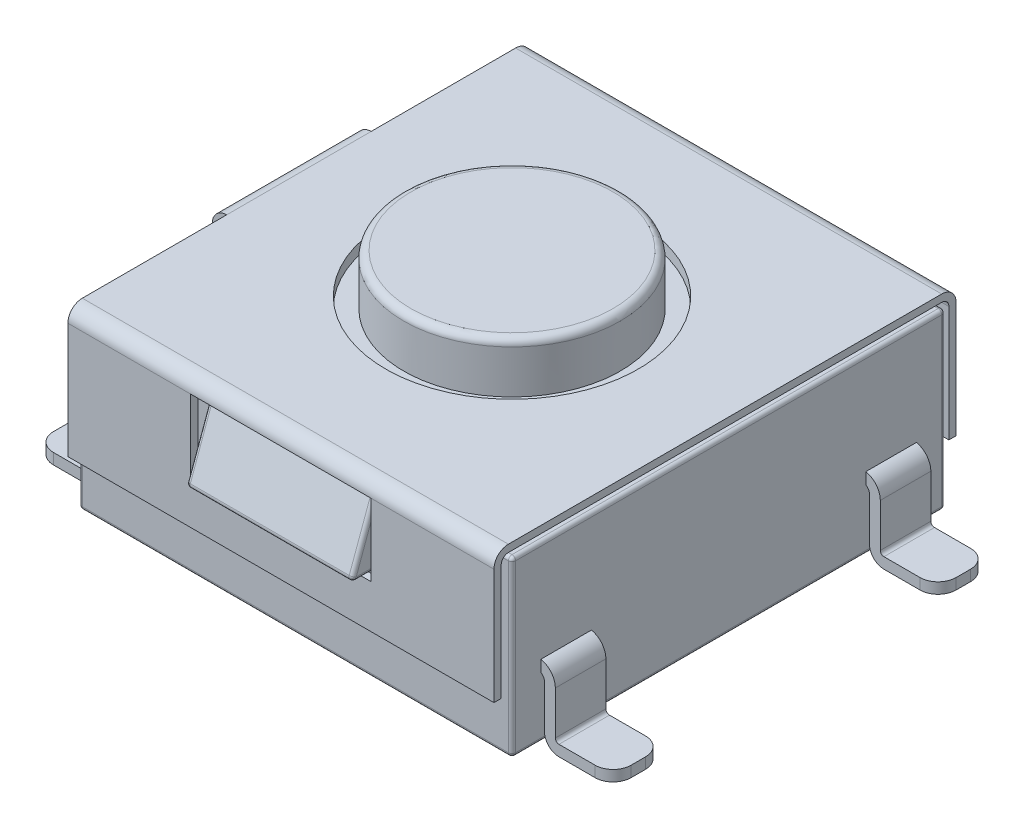
SolidWorks part; units mm, degrees
ref_plane "Front Plane" through (0, 0, 0) normal (0, 0, 1) x (1, 0, 0)
ref_plane "Top Plane" through (0, 0, 0) normal (0, 1, 0) x (1, 0, 0)
ref_plane "Right Plane" through (0, 0, 0) normal (1, 0, 0) x (0, 0, -1)
sketch "Sketch1" plane through (0, 0, 0) normal (0, 1, 0) x (1, 0, 0)
  line L1 (-3, -3) -> (3, -3)
  line L2 (-3, -3) -> (-3, 3)
  line L3 (-3, 3) -> (3, 3)
  line L4 (3, -3) -> (3, 3)
  line L5 (-3, -3) -> (3, 3) construction
  line L6 (-3, 3) -> (3, -3) construction
  point P0 (0, 0)
  dimension "D1" = 6
  dimension "D2" = 6
extrude "Boss-Extrude1" add sketch "Sketch1" along normal blind 2.4
sketch "Sketch2" plane through (0, 0, 0) normal (0, 0, 1) x (1, 0, 0)
  line L0 (-4, -0.05) -> (-3.25, -0.05)
  line L1 (-3.05, 0.15) -> (-3.05, 2.35)
  line L2 (-2.95, 2.45) -> (2.95, 2.45)
  line L3 (3.05, 2.35) -> (3.05, 0.15)
  line L4 (3.25, -0.05) -> (4, -0.05)
  line L5 (-3, 2.4) -> (-3, 0) construction
  line L6 (3, 2.4) -> (3, 0) construction
  line L7 (-3, 2.4) -> (3, 2.4) construction
  line L8 (-4, 0.05) -> (-3.25, 0.05)
  line L9 (-3.15, 0.15) -> (-3.15, 2.35)
  line L10 (-2.95, 2.55) -> (2.95, 2.55)
  line L11 (3.15, 2.35) -> (3.15, 0.15)
  line L12 (3.25, 0.05) -> (4, 0.05)
  line L13 (-4, 0.05) -> (-4, -0.05)
  line L14 (4, 0.05) -> (4, -0.05)
  arc A0 (2.95, 2.45) -> (3.05, 2.35) centre (2.95, 2.35) cw
  arc A1 (-3.05, 2.35) -> (-2.95, 2.45) centre (-2.95, 2.35) cw
  arc A2 (3.05, 0.15) -> (3.25, -0.05) centre (3.25, 0.15) ccw
  arc A3 (-3.25, -0.05) -> (-3.05, 0.15) centre (-3.25, 0.15) ccw
  arc A4 (-3.25, 0.05) -> (-3.15, 0.15) centre (-3.25, 0.15) ccw
  arc A5 (-3.15, 2.35) -> (-2.95, 2.55) centre (-2.95, 2.35) cw
  arc A6 (2.95, 2.55) -> (3.15, 2.35) centre (2.95, 2.35) cw
  arc A7 (3.15, 0.15) -> (3.25, 0.05) centre (3.25, 0.15) ccw
  dimension "D4" = 0.1
  dimension "D5" = 0.2
  dimension "D1" = 0.05
  dimension "D2" = 0.05
  dimension "D3" = 0.05
  dimension "D6" = 2.5
  dimension "D8" = 8
  dimension "D7" = 0.1
extrude "Boss-Extrude2" add sketch "Sketch2" along normal mid plane 6 separate body
sketch "Sketch3" plane through (0, 2.55, 0) normal (0, 1, 0) x (1, 0, 0)
  circle A0 centre (0, 0) radius 1.75
  dimension "D1" = 3.5
extrude "Cut-Extrude1" cut sketch "Sketch3" against normal blind 0.1
sketch "Sketch12" plane through (0, 2.55, 0) normal (0, 1, 0) x (1, 0, 0)
  circle A0 centre (0, 0) radius 1.75 construction
  circle A1 centre (0, 0) radius 1.75
  circle A2 centre (0, 0) radius 1.85
  dimension "D1" = 0.1
extrude "Boss-Extrude7" add sketch "Sketch12" against normal up to surface (0.15 mm away) up to face at (0, 2.4, 0)
sketch "Sketch4" plane through (0, 2.4, 0) normal (0, 1, 0) x (1, 0, 0)
  circle A0 centre (0, 0) radius 1.5
  circle A1 centre (0, 0) radius 1.75 construction
  dimension "D1" = 3
extrude "Boss-Extrude3" add sketch "Sketch4" along normal blind 0.7
fillet "Fillet1" radius 0.1 1 edges at (0, 3.1, 1.5)
sketch "Sketch7" plane through (0, 0, 3) normal (0, 0, 1) x (1, 0, 0)
  line L6 (2.95, 2.55) -> (2.95, 2.45)
  line L14 (-4, 0.05) -> (-4, -0.05)
  line L15 (-2.95, 2.45) -> (2.95, 2.45)
  line L16 (3.05, 2.35) -> (3.05, 0.15)
  line L17 (3.25, -0.05) -> (4, -0.05)
  line L18 (4, -0.05) -> (4, 0.05)
  line L19 (4, 0.05) -> (3.25, 0.05)
  line L20 (3.15, 0.15) -> (3.15, 2.35)
  line L21 (2.95, 2.55) -> (-2.95, 2.55)
  line L24 (3.05, 2.35) -> (3.05, 0.15)
  line L25 (3.25, -0.05) -> (4, -0.05)
  line L26 (4, -0.05) -> (4, 0.05)
  line L27 (4, 0.05) -> (3.25, 0.05)
  line L28 (3.15, 0.15) -> (3.15, 2.35)
  line L33 (-4, -0.05) -> (-3.25, -0.05)
  line L35 (-3.05, 0.15) -> (-3.05, 2.35)
  line L37 (-3.15, 2.35) -> (-3.15, 0.15)
  line L39 (-3.25, 0.05) -> (-4, 0.05)
  arc A8 (3.05, 2.35) -> (2.95, 2.45) centre (2.95, 2.35) ccw
  arc A9 (3.05, 0.15) -> (3.25, -0.05) centre (3.25, 0.15) ccw
  arc A10 (3.15, 0.15) -> (3.25, 0.05) centre (3.25, 0.15) ccw
  arc A11 (3.15, 2.35) -> (2.95, 2.55) centre (2.95, 2.35) ccw
  arc A12 (3.05, 2.35) -> (2.95, 2.45) centre (2.95, 2.35) ccw
  arc A13 (3.05, 0.15) -> (3.25, -0.05) centre (3.25, 0.15) ccw
  arc A14 (3.15, 0.15) -> (3.25, 0.05) centre (3.25, 0.15) ccw
  arc A15 (3.15, 2.35) -> (2.95, 2.55) centre (2.95, 2.35) ccw
  arc A20 (-3.25, -0.05) -> (-3.05, 0.15) centre (-3.25, 0.15) ccw
  arc A22 (-2.95, 2.45) -> (-3.05, 2.35) centre (-2.95, 2.35) ccw
  arc A24 (-2.95, 2.55) -> (-3.15, 2.35) centre (-2.95, 2.35) ccw
  arc A26 (-3.25, 0.05) -> (-3.15, 0.15) centre (-3.25, 0.15) ccw
  dimension "D1" = 0
extrude "Cut-Extrude4" cut sketch "Sketch7" against normal through all
sketch "Sketch6" plane through (0, 0, 3) normal (0, 0, 1) x (1, 0, 0)
  line L0 (-2.95, 2.45) -> (-2.95, 2.55)
  line L10 (2.95, 2.45) -> (2.95, 2.55)
  line L12 (-4, 0.05) -> (-4, -0.05)
  line L13 (-4, -0.05) -> (-3.25, -0.05)
  line L14 (-3.05, 0.15) -> (-3.05, 2.35)
  line L15 (-2.95, 2.45) -> (2.95, 2.45)
  line L21 (2.95, 2.55) -> (-2.95, 2.55)
  line L22 (-3.15, 2.35) -> (-3.15, 0.15)
  line L23 (-3.25, 0.05) -> (-4, 0.05)
  line L24 (-4, 0.05) -> (-4, -0.05)
  line L25 (-4, -0.05) -> (-3.25, -0.05)
  line L26 (-3.05, 0.15) -> (-3.05, 2.35)
  line L34 (-3.15, 2.35) -> (-3.15, 0.15)
  line L35 (-3.25, 0.05) -> (-4, 0.05)
  arc A8 (-3.25, -0.05) -> (-3.05, 0.15) centre (-3.25, 0.15) ccw
  arc A9 (-2.95, 2.45) -> (-3.05, 2.35) centre (-2.95, 2.35) ccw
  arc A14 (-2.95, 2.55) -> (-3.15, 2.35) centre (-2.95, 2.35) ccw
  arc A15 (-3.25, 0.05) -> (-3.15, 0.15) centre (-3.25, 0.15) ccw
  arc A16 (-3.25, -0.05) -> (-3.05, 0.15) centre (-3.25, 0.15) ccw
  arc A17 (-2.95, 2.45) -> (-3.05, 2.35) centre (-2.95, 2.35) ccw
  arc A22 (-2.95, 2.55) -> (-3.15, 2.35) centre (-2.95, 2.35) ccw
  arc A23 (-3.25, 0.05) -> (-3.15, 0.15) centre (-3.25, 0.15) ccw
  dimension "D1" = 0
extrude "Cut-Extrude3" cut sketch "Sketch6" against normal blind 2
sketch "Sketch5" plane through (-3.05, 0, 0) normal (1, 0, 0) x (0, 0, -1)
  line L1 (-1, -0.05) -> (3, -0.05) construction
  line L2 (-0.35, -0.05) -> (-1, -0.05)
  line L3 (-0.35, -0.05) -> (-0.35, 0.75)
  line L4 (-0.55, 0.95) -> (-1, 0.95)
  line L5 (-1, -0.05) -> (-1, 0.95)
  line L6 (-1, 2.35) -> (-1, 0.15) construction
  arc A0 (-0.35, 0.75) -> (-0.55, 0.95) centre (-0.55, 0.75) ccw
  dimension "D3" = 0.2
  dimension "D1" = 0.35
  dimension "D2" = 1
extrude "Cut-Extrude2" cut sketch "Sketch5" against normal through all
ref_plane "Plane1" through (0, 0, 2.25) normal (0, 0, 1) x (1, 0, 0)
sketch "Sketch11" plane through (0, 0, 2.25) normal (0, 0, 1) x (1, 0, 0)
  line L0 (-4, -0.05) -> (-3.25, -0.05)
  line L1 (-3.05, 0.15) -> (-3.05, 0.75)
  line L2 (-3.05, 0.75) -> (-3.05, 0.95) construction
  line L3 (-2.95, 0.85) -> (2.95, 0.85)
  line L4 (3.05, 0.75) -> (3.05, 0.15)
  line L5 (3.25, -0.05) -> (4, -0.05)
  line L9 (-4, 0.1) -> (-3.25, 0.1)
  line L10 (-3.2, 0.15) -> (-3.2, 0.75)
  line L11 (-2.95, 1) -> (2.95, 1)
  line L12 (3.2, 0.75) -> (3.2, 0.15)
  line L13 (3.25, 0.1) -> (4, 0.1)
  line L14 (4, 0.1) -> (4, -0.05)
  line L15 (-4, 0.1) -> (-4, -0.05)
  arc A0 (3.05, 0.15) -> (3.25, -0.05) centre (3.25, 0.15) ccw
  arc A1 (-3.25, -0.05) -> (-3.05, 0.15) centre (-3.25, 0.15) ccw
  arc A2 (-3.05, 0.75) -> (-2.95, 0.85) centre (-2.95, 0.75) cw
  arc A3 (2.95, 0.85) -> (3.05, 0.75) centre (2.95, 0.75) cw
  arc A4 (-3.25, 0.1) -> (-3.2, 0.15) centre (-3.25, 0.15) ccw
  arc A5 (-3.2, 0.75) -> (-2.95, 1) centre (-2.95, 0.75) cw
  arc A6 (2.95, 1) -> (3.2, 0.75) centre (2.95, 0.75) cw
  arc A7 (3.2, 0.15) -> (3.25, 0.1) centre (3.25, 0.15) ccw
  point P16 (-3.05, 0.85)
  dimension "D3" = 0.2
  dimension "D4" = 0.1
  dimension "D1" = 8
  dimension "D5" = 0.15
extrude "Boss-Extrude6" add sketch "Sketch11" along normal mid plane 0.7
fillet "Fillet2" radius 0.25 6 edges at (-3.1, 0.95, 1) (-4, 0, 0.35) (4, 0.025, 1.9) (4, 0.025, 2.6) (-4, 0.025, 1.9) (-4, 0.025, 2.6)
mirror "Mirror1" about plane through (0, 0, 0) normal (0, 0, 1) of "Fillet2", "Boss-Extrude6", "Cut-Extrude2", "Cut-Extrude3"
sketch "Sketch8" plane through (0, 0, 0) normal (1, 0, 0) x (0, 0, -1)
  line L0 (3.1, 2.35) -> (3.1, 0.75)
  line L1 (3.1, 0.75) -> (3.2, 0.75)
  line L2 (3.2, 0.75) -> (3.2, 2.35)
  line L3 (3, 2.55) -> (3, 2.45)
  line L6 (0, 2.45) -> (0, 0) construction
  line L7 (-3, 2.55) -> (3, 2.55) construction
  line L8 (-3, 2.45) -> (3, 2.45) construction
  line L9 (3, 2.55) -> (3, 2.45) construction
  line L10 (-3, 2.55) -> (-3, 2.45)
  line L11 (-3.2, 0.75) -> (-3.2, 2.35)
  line L12 (-3.1, 0.75) -> (-3.2, 0.75)
  line L13 (-3.1, 2.35) -> (-3.1, 0.75)
  arc A0 (3, 2.45) -> (3.1, 2.35) centre (3, 2.35) cw
  arc A1 (3, 2.55) -> (3.2, 2.35) centre (3, 2.35) cw
  arc A2 (-3, 2.55) -> (-3.2, 2.35) centre (-3, 2.35) ccw
  arc A3 (-3, 2.45) -> (-3.1, 2.35) centre (-3, 2.35) ccw
  dimension "D1" = 0.1
  dimension "D2" = 1.8
extrude "Boss-Extrude4" add sketch "Sketch8" against normal up to surface and the other way up to surface up to face at (-2.95, 2.5, -2) other way up to face at (2.95, 2.5, 0)
sketch "Sketch9" plane through (0, 0, 3.2) normal (0, 0, 1) x (1, 0, 0)
  line L1 (-1.25, 1.35) -> (1.25, 1.35)
  line L2 (-1.25, 1.35) -> (-1.25, 2.35)
  line L3 (-1.25, 2.35) -> (1.25, 2.35)
  line L4 (1.25, 1.35) -> (1.25, 2.35)
  line L5 (-1.25, 1.35) -> (1.25, 2.35) construction
  line L6 (-1.25, 2.35) -> (1.25, 1.35) construction
  line L7 (-2.95, 2.35) -> (2.95, 2.35) construction
  point P0 (0, 1.85)
  dimension "D1" = 2.5
  dimension "D2" = 1
extrude "Cut-Extrude5" cut sketch "Sketch9" against normal blind 0.1
mirror "Mirror2" about plane through (0, 0, 0) normal (0, 0, 1) of "Cut-Extrude5"
sketch "Sketch10" plane through (0, 0, 0) normal (1, 0, 0) x (0, 0, -1)
  line L0 (3, 2.4) -> (3.3785, 1.36)
  line L1 (3, 2.4) -> (3, 0) construction
  line L2 (3.3785, 1.36) -> (3, 1.36)
  line L3 (3, 1.36) -> (3, 2.4)
  line L5 (0, 0) -> (0, 2.4) construction
  line L7 (-3, 1.36) -> (-3, 2.4)
  line L8 (-3.3785, 1.36) -> (-3, 1.36)
  line L9 (-3, 2.4) -> (-3.3785, 1.36)
  line L10 (3.1, 1.35) -> (3.2, 1.35) construction
  line L11 (-3, 2.4) -> (3, 2.4) construction
  dimension "D2" = 0.01
  dimension "D3" = 20
extrude "Boss-Extrude5" add sketch "Sketch10" along normal mid plane 2.3
fillet "Fillet4" radius 0.05 20 edges at (0, 1.36, 3.3785) (0, 1.36, -3.3785) (-3, 1.2, 3) (-3, 2.4, 0) (3, 1.2, -3) (3, 2.4, 0) (3, 1.2, 3) (3, 0, 0) (0, 0, 3) (-3, 0, 0) (0, 0, -3) (-3, 1.2, -3) (-1.15, 1.36, -3.1893) (1.15, 1.36, -3.1893) (-1.15, 1.36, 3.1893) (1.15, 1.36, 3.1893) tangent propagation no
fillet "Fillet5" radius 0.05 8 edges at (-2.9854, 2.3854, -2.9854) (2.9854, 2.3854, -2.9854) (2.9854, 2.3854, 2.9854) (-2.9854, 2.3854, 2.9854) tangent propagation no
